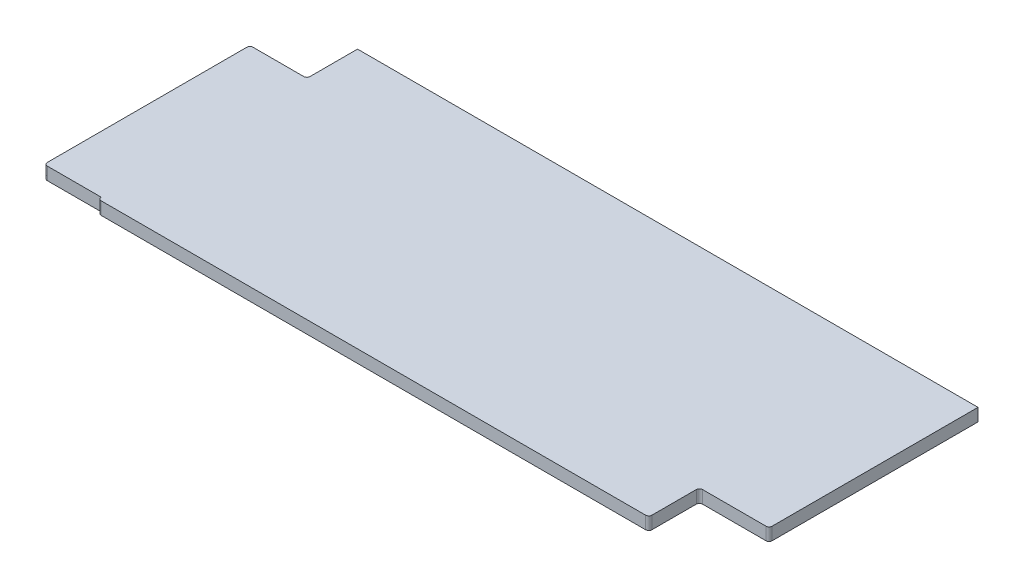
SolidWorks part; units mm, degrees
ref_plane "前视基准面" through (0, 0, 0) normal (0, 0, 1) x (1, 0, 0)
ref_plane "上视基准面" through (0, 0, 0) normal (0, 1, 0) x (1, 0, 0)
ref_plane "右视基准面" through (0, 0, 0) normal (1, 0, 0) x (0, 0, -1)
sketch "草图1" plane through (0, 0, 0) normal (0, 1, 0) x (1, 0, 0)
  line L0 (0, 0) -> (0, -82)
  line L1 (0, 0) -> (-196, 0)
  line L2 (-196, 0) -> (-196, -82)
  line L3 (-196, -82) -> (0, -82)
  line L4 (-22, -82) -> (-22, -66)
  line L5 (-22, -66) -> (0, -66)
  dimension "D1" = 82
  dimension "D2" = 196
  dimension "D3" = 16
  dimension "D4" = 22
extrude "凸台-拉伸1" add sketch "草图1" along normal blind 4 contours L4 L5 L0 L1 L2 L3 region at (-99.9481, 0, 40.2611)
sketch "草图2" plane through (0, 4, 0) normal (0, 1, 0) x (1, 0, 0)
  line L0 (-196, 0) -> (-196, -82) construction
  line L1 (-196, -16) -> (-214, -16)
  line L2 (-196, -16) -> (-196, -81)
  line L3 (-196, -81) -> (-214, -81)
  line L4 (-214, -16) -> (-214, -81)
  line L5 (0, 0) -> (-196, 0) construction
  dimension "D1" = 18
  dimension "D2" = 16
extrude "凸台-拉伸2" add sketch "草图2" against normal up to surface (4 mm away) up to face at (-72.6667, 0, 49.3333)
fillet "圆角1" radius 1 7 edges at (-196, 2, 82) (0, 2, 66) (-22, 2, 82) (-22, 2, 66) (-214, 2, 81) (-214, 2, 16) (-196, 2, 16)
